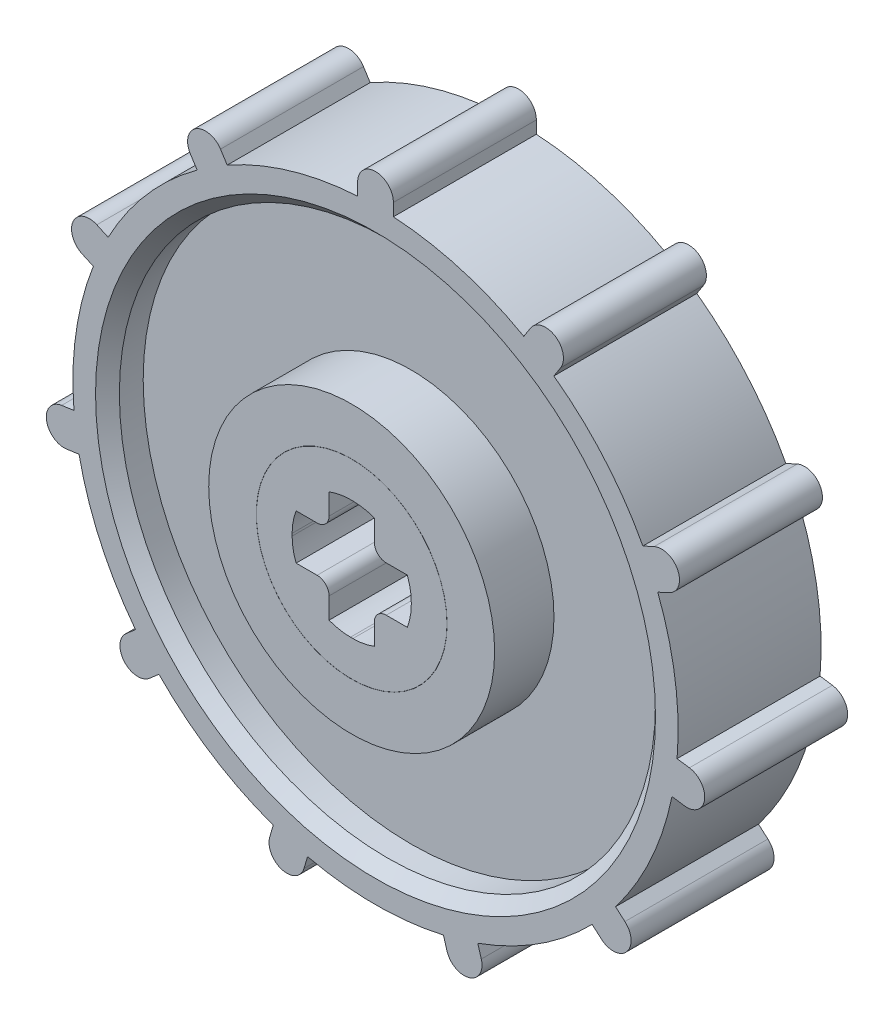
SolidWorks part; units mm, degrees
ref_plane "Front Plane" through (0, 0, 0) normal (0, 0, 1) x (1, 0, 0)
ref_plane "Top Plane" through (0, 0, 0) normal (0, 1, 0) x (1, 0, 0)
ref_plane "Right Plane" through (0, 0, 0) normal (1, 0, 0) x (0, 0, -1)
sketch "Sketch1" plane through (0, 0, 0) normal (1, 0, 0) x (0, 0, -1)
  line L0 (0, 12.7) -> (7, 12.7)
  line L1 (7, 12.7) -> (7, 11.7)
  line L2 (6.5, 0) -> (0, 0)
  line L3 (0, 0) -> (0, 12.7)
  line L5 (-9.434, 0) -> (0, 0) construction
  line L6 (7, 11.7) -> (6.5, 11.7)
  line L7 (6.5, 11.7) -> (6.5, 0)
  dimension "D1" = 12.7
  dimension "D2" = 7
  dimension "D3" = 0.5
  dimension "D4" = 1
revolve "Revolve1" add sketch "Sketch1" angle 360 about L5
sketch "Sketch2" plane through (0, 0, 0) normal (0, 0, 1) x (1, 0, 0)
  line L0 (0, 12.6778) -> (0, 13.2) construction
  line L1 (-0.75, 12.6778) -> (-0.75, 13.2)
  line L2 (0.75, 12.6778) -> (0.75, 13.2)
  circle A0 centre (0, 0) radius 12.7 construction
  arc A1 (-0.75, 12.6778) -> (0.75, 12.6778) centre (0, 12.6778) ccw
  arc A2 (0.75, 13.2) -> (-0.75, 13.2) centre (0, 13.2) ccw
  point P2 (0, 0)
  point P5 (0, 0)
  point P6 (0, 12.9389)
  point P11 (0, 12.7)
  point P12 (0, 0)
  dimension "D1" = 0.75
  dimension "D2" = 0.5
extrude "Boss-Extrude1" add sketch "Sketch2" against normal up to surface (7 mm away) up to face at (12.7, 0, -7)
pattern_circular "CirPattern1" count 11 over 360 about axis through (0, 0, 9.434) along (0, 0, 1) of "Boss-Extrude1" reverse direction yes
sketch "Sketch3" plane through (0, 0, 0) normal (0, 0, 1) x (1, 0, 0)
  line L0 (-0.95, 2.3324) -> (-0.95, 1.45)
  line L1 (-0.95, 0.95) -> (0, 0) construction
  line L2 (0, 0) -> (0, 2.5) construction
  line L3 (-0.05, 2.5) -> (0.05, 2.5)
  line L4 (-2.5, 0.05) -> (-2.5, -0.05)
  line L5 (-2.3324, 0.95) -> (-1.45, 0.95)
  line L6 (2.5, 0.05) -> (2.5, -0.05)
  line L7 (2.3324, 0.95) -> (1.45, 0.95)
  line L8 (0.95, 2.3324) -> (0.95, 1.45)
  line L9 (-2.5, 0) -> (0, 0) construction
  line L10 (-2.3324, -0.95) -> (-1.45, -0.95)
  line L11 (-0.95, -2.3324) -> (-0.95, -1.45)
  line L12 (-0.05, -2.5) -> (0.05, -2.5)
  line L13 (0.95, -2.3324) -> (0.95, -1.45)
  line L14 (2.3324, -0.95) -> (1.45, -0.95)
  arc A0 (-0.05, 2.5) -> (-0.95, 2.3324) centre (-0.05, 0) ccw
  arc A1 (-2.5, 0.05) -> (-2.3324, 0.95) centre (0, 0.05) cw
  arc A2 (2.5, 0.05) -> (2.3324, 0.95) centre (0, 0.05) ccw
  arc A3 (0.05, 2.5) -> (0.95, 2.3324) centre (0.05, 0) cw
  arc A4 (-2.5, -0.05) -> (-2.3324, -0.95) centre (0, -0.05) ccw
  arc A5 (-0.05, -2.5) -> (-0.95, -2.3324) centre (-0.05, 0) cw
  arc A6 (0.05, -2.5) -> (0.95, -2.3324) centre (0.05, 0) ccw
  arc A7 (2.5, -0.05) -> (2.3324, -0.95) centre (0, -0.05) cw
  arc A8 (-1.45, -0.95) -> (-0.95, -1.45) centre (-1.45, -1.45) cw
  arc A9 (0.95, -1.45) -> (1.45, -0.95) centre (1.45, -1.45) cw
  arc A10 (1.45, 0.95) -> (0.95, 1.45) centre (1.45, 1.45) cw
  arc A11 (-0.95, 1.45) -> (-1.45, 0.95) centre (-1.45, 1.45) cw
  point P33 (2.5, 0)
  point P35 (-0.95, -0.95)
  point P38 (0.95, -0.95)
  point P41 (0.95, 0.95)
  dimension "D4" = 2.5
  dimension "D5" = 0.5
  dimension "D1" = 1.9
  dimension "D2" = 0.1
  dimension "D3" = 5
extrude "Cut-Extrude1" cut sketch "Sketch3" against normal blind 5
sketch "Sketch4" plane through (0, 0, 0) normal (0, 0, 1) x (1, 0, 0)
  circle A0 centre (0, 0) radius 4
  circle A1 centre (0, 0) radius 11.25
  dimension "D1" = 8
  dimension "D2" = 22.5
extrude "Cut-Extrude2" cut sketch "Sketch4" against normal blind 2.5
sketch "Sketch5" plane through (0, 0, 0) normal (0, 0, 1) x (1, 0, 0)
  circle A0 centre (0, 0) radius 4.005
  circle A1 centre (0, 0) radius 6
  dimension "D1" = 12
  dimension "D2" = 8.01
extrude "Boss-Extrude2" add sketch "Sketch5" against normal blind 2.49 separate body
sketch "Sketch6" plane through (0, 0, 0) normal (0, 0, 1) x (1, 0, 0)
  line L22 (-6.2232, 11.0708) -> (-6.5055, 11.51)
  line L23 (-7.7674, 10.6991) -> (-7.4851, 10.2598)
  line L24 (-11.2206, 5.9488) -> (-11.6956, 6.1657)
  line L25 (-12.3187, 4.8013) -> (-11.8437, 4.5843)
  line L26 (-12.6555, -1.0619) -> (-13.1724, -1.1362)
  line L27 (-12.9589, -2.6209) -> (-12.4421, -2.5466)
  line L28 (-10.0724, -7.7354) -> (-10.467, -8.0773)
  line L29 (-9.4847, -9.211) -> (-9.0901, -8.869)
  line L30 (-4.2914, -11.953) -> (-4.4385, -12.454)
  line L31 (-2.9993, -12.8766) -> (-2.8521, -12.3756)
  line L32 (2.8521, -12.3756) -> (2.9993, -12.8766)
  line L33 (4.4385, -12.454) -> (4.2914, -11.953)
  line L34 (9.0901, -8.869) -> (9.4847, -9.211)
  line L35 (10.467, -8.0773) -> (10.0724, -7.7354)
  line L36 (12.4421, -2.5466) -> (12.9589, -2.6209)
  line L37 (13.1724, -1.1362) -> (12.6555, -1.0619)
  line L38 (11.8437, 4.5843) -> (12.3187, 4.8013)
  line L39 (11.6956, 6.1657) -> (11.2206, 5.9488)
  line L40 (7.4851, 10.2598) -> (7.7674, 10.6991)
  line L41 (6.5055, 11.51) -> (6.2232, 11.0708)
  line L42 (0.75, 12.6778) -> (0.75, 13.2)
  line L43 (-0.75, 13.2) -> (-0.75, 12.6778)
  line L44 (-6.2232, 11.0708) -> (-6.5055, 11.51)
  line L45 (-7.7674, 10.6991) -> (-7.4851, 10.2598)
  line L46 (-11.2206, 5.9488) -> (-11.6956, 6.1657)
  line L47 (-12.3187, 4.8013) -> (-11.8437, 4.5843)
  line L48 (-12.6555, -1.0619) -> (-13.1724, -1.1362)
  line L49 (-12.9589, -2.6209) -> (-12.4421, -2.5466)
  line L50 (-10.0724, -7.7354) -> (-10.467, -8.0773)
  line L51 (-9.4847, -9.211) -> (-9.0901, -8.869)
  line L52 (-4.2914, -11.953) -> (-4.4385, -12.454)
  line L53 (-2.9993, -12.8766) -> (-2.8521, -12.3756)
  line L54 (2.8521, -12.3756) -> (2.9993, -12.8766)
  line L55 (4.4385, -12.454) -> (4.2914, -11.953)
  line L56 (9.0901, -8.869) -> (9.4847, -9.211)
  line L57 (10.467, -8.0773) -> (10.0724, -7.7354)
  line L58 (12.4421, -2.5466) -> (12.9589, -2.6209)
  line L59 (13.1724, -1.1362) -> (12.6555, -1.0619)
  line L60 (11.8437, 4.5843) -> (12.3187, 4.8013)
  line L61 (11.6956, 6.1657) -> (11.2206, 5.9488)
  line L62 (7.4851, 10.2598) -> (7.7674, 10.6991)
  line L63 (6.5055, 11.51) -> (6.2232, 11.0708)
  line L64 (0.75, 12.6778) -> (0.75, 13.2)
  line L65 (-0.75, 13.2) -> (-0.75, 12.6778)
  circle A0 centre (0, 0) radius 11.25 construction
  circle A1 centre (0, 0) radius 11.25
  arc A22 (-0.75, 12.6778) -> (-6.2232, 11.0708) centre (0, 0) ccw
  arc A23 (-6.5055, 11.51) -> (-7.7674, 10.6991) centre (-7.1365, 11.1045) ccw
  arc A24 (-7.4851, 10.2598) -> (-11.2206, 5.9488) centre (0, 0) ccw
  arc A25 (-11.6956, 6.1657) -> (-12.3187, 4.8013) centre (-12.0071, 5.4835) ccw
  arc A26 (-11.8437, 4.5843) -> (-12.6555, -1.0619) centre (0, 0) ccw
  arc A27 (-13.1724, -1.1362) -> (-12.9589, -2.6209) centre (-13.0656, -1.8786) ccw
  arc A28 (-12.4421, -2.5466) -> (-10.0724, -7.7354) centre (0, 0) ccw
  arc A29 (-10.467, -8.0773) -> (-9.4847, -9.211) centre (-9.9759, -8.6442) ccw
  arc A30 (-9.0901, -8.869) -> (-4.2914, -11.953) centre (0, 0) ccw
  arc A31 (-4.4385, -12.454) -> (-2.9993, -12.8766) centre (-3.7189, -12.6653) ccw
  arc A32 (-2.8521, -12.3756) -> (2.8521, -12.3756) centre (0, 0) ccw
  arc A33 (2.9993, -12.8766) -> (4.4385, -12.454) centre (3.7189, -12.6653) ccw
  arc A34 (4.2914, -11.953) -> (9.0901, -8.869) centre (0, 0) ccw
  arc A35 (9.4847, -9.211) -> (10.467, -8.0773) centre (9.9759, -8.6442) ccw
  arc A36 (10.0724, -7.7354) -> (12.4421, -2.5466) centre (0, 0) ccw
  arc A37 (12.9589, -2.6209) -> (13.1724, -1.1362) centre (13.0656, -1.8786) ccw
  arc A38 (12.6555, -1.0619) -> (11.8437, 4.5843) centre (0, 0) ccw
  arc A39 (12.3187, 4.8013) -> (11.6956, 6.1657) centre (12.0071, 5.4835) ccw
  arc A40 (11.2206, 5.9488) -> (7.4851, 10.2598) centre (0, 0) ccw
  arc A41 (7.7674, 10.6991) -> (6.5055, 11.51) centre (7.1365, 11.1045) ccw
  arc A42 (6.2232, 11.0708) -> (0.75, 12.6778) centre (0, 0) ccw
  arc A43 (0.75, 13.2) -> (-0.75, 13.2) centre (0, 13.2) ccw
  arc A44 (-0.75, 12.6778) -> (-6.2232, 11.0708) centre (0, 0) ccw
  arc A45 (-6.5055, 11.51) -> (-7.7674, 10.6991) centre (-7.1365, 11.1045) ccw
  arc A46 (-7.4851, 10.2598) -> (-11.2206, 5.9488) centre (0, 0) ccw
  arc A47 (-11.6956, 6.1657) -> (-12.3187, 4.8013) centre (-12.0071, 5.4835) ccw
  arc A48 (-11.8437, 4.5843) -> (-12.6555, -1.0619) centre (0, 0) ccw
  arc A49 (-13.1724, -1.1362) -> (-12.9589, -2.6209) centre (-13.0656, -1.8786) ccw
  arc A50 (-12.4421, -2.5466) -> (-10.0724, -7.7354) centre (0, 0) ccw
  arc A51 (-10.467, -8.0773) -> (-9.4847, -9.211) centre (-9.9759, -8.6442) ccw
  arc A52 (-9.0901, -8.869) -> (-4.2914, -11.953) centre (0, 0) ccw
  arc A53 (-4.4385, -12.454) -> (-2.9993, -12.8766) centre (-3.7189, -12.6653) ccw
  arc A54 (-2.8521, -12.3756) -> (2.8521, -12.3756) centre (0, 0) ccw
  arc A55 (2.9993, -12.8766) -> (4.4385, -12.454) centre (3.7189, -12.6653) ccw
  arc A56 (4.2914, -11.953) -> (9.0901, -8.869) centre (0, 0) ccw
  arc A57 (9.4847, -9.211) -> (10.467, -8.0773) centre (9.9759, -8.6442) ccw
  arc A58 (10.0724, -7.7354) -> (12.4421, -2.5466) centre (0, 0) ccw
  arc A59 (12.9589, -2.6209) -> (13.1724, -1.1362) centre (13.0656, -1.8786) ccw
  arc A60 (12.6555, -1.0619) -> (11.8437, 4.5843) centre (0, 0) ccw
  arc A61 (12.3187, 4.8013) -> (11.6956, 6.1657) centre (12.0071, 5.4835) ccw
  arc A62 (11.2206, 5.9488) -> (7.4851, 10.2598) centre (0, 0) ccw
  arc A63 (7.7674, 10.6991) -> (6.5055, 11.51) centre (7.1365, 11.1045) ccw
  arc A64 (6.2232, 11.0708) -> (0.75, 12.6778) centre (0, 0) ccw
  arc A65 (0.75, 13.2) -> (-0.75, 13.2) centre (0, 13.2) ccw
  dimension "D1" = 0
extrude "Cut-Extrude3" cut sketch "Sketch6" against normal blind 1
chamfer "Chamfer1" distance 0.5 angle 45 1 edges at (11.25, 0, -1)
